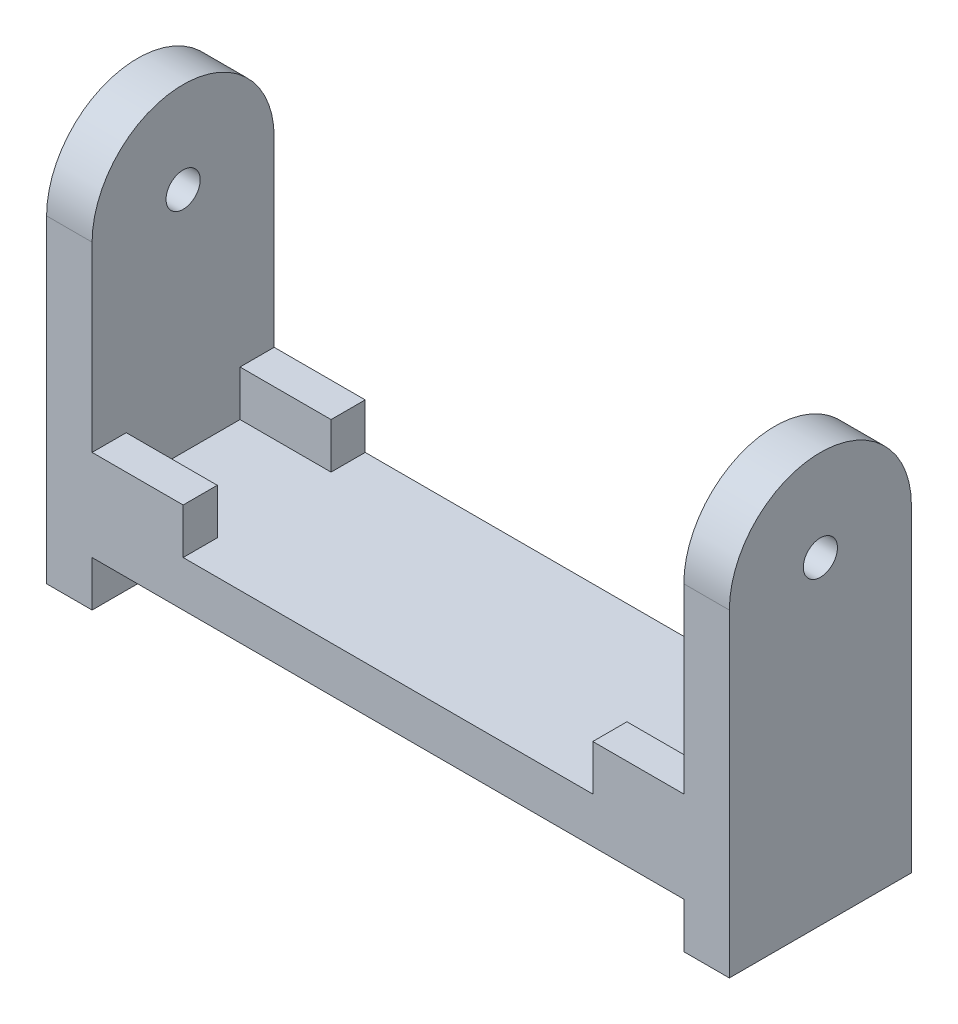
SolidWorks part; units mm, degrees
ref_plane "前基準面" through (0, 0, 0) normal (0, 0, 1) x (1, 0, 0)
ref_plane "上基準面" through (0, 0, 0) normal (0, 1, 0) x (1, 0, 0)
ref_plane "右基準面" through (0, 0, 0) normal (1, 0, 0) x (0, 0, -1)
sketch "草圖2" plane through (0, 0, 0) normal (1, 0, 0) x (0, 0, -1)
  line L0 (-40, 0) -> (-40, -120)
  line L1 (-40, -120) -> (40, -120)
  line L2 (40, -120) -> (40, 0)
  line L3 (0, 122.7537) -> (0, -552.4626) construction
  circle A0 centre (0, 0) radius 7.5
  arc A1 (40, 0) -> (-40, 0) centre (0, 0) ccw
  dimension "D1" = 15
  dimension "D3" = 40
  dimension "D2" = 120
extrude "填料-伸長1" add sketch "草圖2" along normal blind 300
sketch "草圖3" plane through (0, 0, -40) normal (0, 0, -1) x (-1, 0, 0)
  line L0 (-280, 40) -> (-280, -100)
  line L1 (0, 40) -> (-300, 40) construction
  line L2 (-280, -100) -> (-20, -100)
  line L3 (-20, -100) -> (-20, 40)
  line L4 (-20, 40) -> (-280, 40)
  line L5 (-300, -120) -> (0, -120) construction
  line L6 (-300, -120) -> (-300, 0) construction
  line L7 (0, -120) -> (0, 0) construction
  dimension "D1" = 20
  dimension "D2" = 20
  dimension "D3" = 20
extrude "除料-伸長1" cut sketch "草圖3" against normal through all
sketch "草圖4" plane through (0, -120, 0) normal (0, -1, 0) x (1, 0, 0)
  line L0 (-11.0995, 0) -> (327.2431, 0) construction
  line L1 (150, 40) -> (150, -40) construction
  line L2 (300, 40) -> (0, 40) construction
  line L3 (300, -40) -> (0, -40) construction
  line L5 (0, 40) -> (20, 40)
  line L6 (0, 40) -> (0, -40)
  line L7 (0, -40) -> (20, -40)
  line L8 (20, 40) -> (20, -40)
  line L9 (300, -40) -> (280, -40)
  line L10 (300, -40) -> (300, 40)
  line L11 (300, 40) -> (280, 40)
  line L12 (280, -40) -> (280, 40)
  dimension "D1" = 20
  dimension "D2" = 20
extrude "填料-伸長2" add sketch "草圖4" along normal blind 20
sketch "草圖5" plane through (0, -140, 0) normal (0, -1, 0) x (1, 0, 0)
  line L0 (-15.8081, 0) -> (313.4538, 0) construction
  line L1 (10, 40) -> (10, -40) construction
  line L2 (20, 40) -> (0, 40) construction
  line L3 (0, -40) -> (20, -40) construction
  line L4 (290, -40) -> (290, 40) construction
  line L5 (280, -40) -> (300, -40) construction
  line L6 (300, 40) -> (280, 40) construction
  circle A0 centre (10, 0) radius 5
  circle A1 centre (290, 0) radius 5
  point P19 (290, 0)
  dimension "D1" = 10
extrude "螺絲預留孔" cut sketch "草圖5" against normal blind 20
sketch "草圖7" plane through (0, -100, 0) normal (0, 1, 0) x (1, 0, 0)
  line L0 (-20.5166, 0) -> (321.5256, 0) construction
  line L1 (20, 40) -> (60, 40)
  line L2 (20, 40) -> (20, 25)
  line L3 (20, 25) -> (60, 25)
  line L4 (60, 40) -> (60, 25)
  line L5 (20, -40) -> (60, -40)
  line L6 (20, -40) -> (20, -25)
  line L7 (20, -25) -> (60, -25)
  line L8 (60, -40) -> (60, -25)
  line L9 (280, -40) -> (240, -40)
  line L10 (280, -40) -> (280, -25)
  line L11 (280, -25) -> (240, -25)
  line L12 (240, -40) -> (240, -25)
  line L13 (280, 40) -> (240, 40)
  line L14 (280, 40) -> (280, 25)
  line L15 (280, 25) -> (240, 25)
  line L16 (240, 40) -> (240, 25)
  line L17 (280, 40) -> (280, -40) construction
  dimension "D1" = 40
  dimension "D2" = 15
  dimension "D3" = 40
extrude "放馬達" add sketch "草圖7" along normal blind 20
